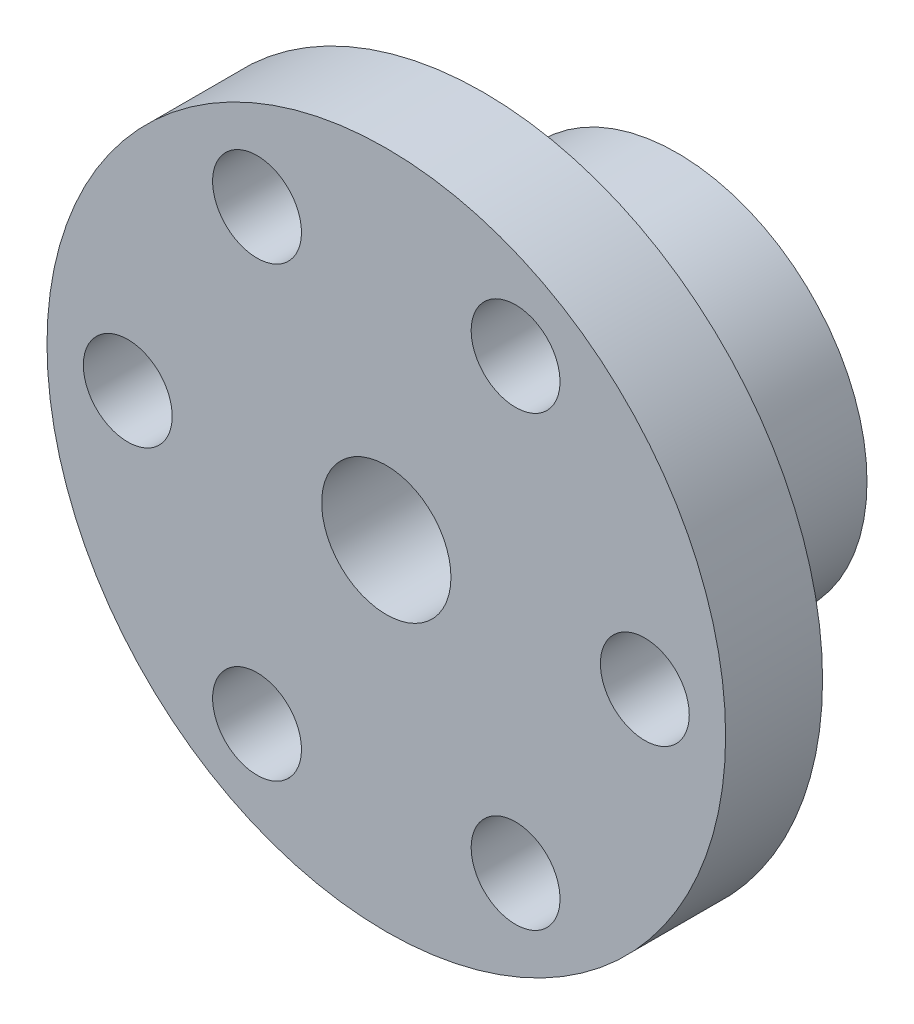
SolidWorks part; units mm, degrees
ref_plane "前视基准面" through (0, 0, 0) normal (0, 0, 1) x (1, 0, 0)
ref_plane "上视基准面" through (0, 0, 0) normal (0, 1, 0) x (1, 0, 0)
ref_plane "右视基准面" through (0, 0, 0) normal (1, 0, 0) x (0, 0, -1)
sketch "草图1" plane through (0, 0, 0) normal (0, 0, 1) x (1, 0, 0)
  line L0 (0, 0) -> (16, 0) construction
  line L1 (0, 0) -> (0, -16) construction
  line L2 (0, 0) -> (11.3137, 11.3137) construction
  line L3 (0, 0) -> (-11.3137, 11.3137) construction
  line L4 (0, 0) -> (6.1229, -14.7821) construction
  line L5 (-8, 13.8564) -> (0, 0) construction
  line L6 (0, 0) -> (8, 13.8564) construction
  line L7 (-16.5, -12.9904) -> (-16.5, 12.9904)
  line L8 (16.5, 12.9904) -> (16.5, -12.9904)
  line L9 (0, 0) -> (1.8478, 0.7654)
  line L10 (1.8478, 0.7654) -> (9.8841, -18.6361)
  line L11 (9.8841, -18.6361) -> (8.0364, -19.4015)
  line L12 (1.4782, 0.6123) -> (7.2185, -13.2459)
  line L13 (7.2185, -13.2459) -> (7.588, -13.0928)
  line L14 (-12.5, -16.8745) -> (-12.5, 16.8745)
  line L15 (12.5, 16.8745) -> (12.5, -16.8745)
  circle A0 centre (0, 0) radius 21
  circle A1 centre (0, 0) radius 16 construction
  circle A2 centre (11.3137, 11.3137) radius 2.75
  circle A3 centre (-11.3137, 11.3137) radius 2.75
  circle A4 centre (0, 16) radius 2.75
  circle A5 centre (-8, 13.8564) radius 2.75
  circle A6 centre (8, 13.8564) radius 2.75
  circle A7 centre (0, 0) radius 4
  point P21 (0, 21)
  dimension "D1" = 90
  dimension "D6" = 42
  dimension "(D4)" = 32
  dimension "D5" = 5.5
  dimension "D2" = 3.2
  dimension "(d)" = 8
  dimension "JD" = 22.5
  dimension "D3" = 60
  dimension "D4" = 6
  dimension "L5" = 33
  dimension "Q" = 4
  dimension "L6" = 25
sketch "草图2" plane through (0, 0, 0) normal (1, 0, 0) x (0, 0, -1)
  line L0 (-3, 0) -> (15, 0) construction
  line L1 (-3, 0) -> (-3, 21)
  line L2 (-3, 21) -> (3, 21)
  line L3 (3, 21) -> (3, 11.75)
  line L4 (3, 11.75) -> (15, 11.75)
  line L5 (15, 11.75) -> (15, 0)
  line L6 (0, 0) -> (0, 21) construction
  line L7 (8, 11.75) -> (8, 0)
  line L8 (-75, 0) -> (75, 0) construction
  line L9 (75, 0) -> (-57, 0)
  dimension "D1" = 23.5
  dimension "L1" = 18
  dimension "L2" = 6
  dimension "L7" = 5
  dimension "ZL" = 150
  dimension "D3" = 132
sketch "草图3" plane through (0, 0, 0) normal (1, 0, 0) x (0, 0, -1)
  line L0 (-3, 0) -> (-3, 21) construction
  line L1 (-3, 21) -> (3, 21) construction
  line L2 (3, 21) -> (3, 11.75) construction
  line L3 (3, 11.75) -> (15, 11.75) construction
  line L4 (15, 11.75) -> (15, 0) construction
  line L5 (-3, 0) -> (-3, 21)
  line L6 (-3, 21) -> (3, 21)
  line L7 (3, 21) -> (3, 11.75)
  line L8 (3, 11.75) -> (15, 11.75)
  line L9 (15, 11.75) -> (15, 0)
  line L10 (-3, 0) -> (15, 0)
revolve "旋转1" add sketch "草图3" angle 360 about L10
sketch "草图13" [suppressed] plane through (0, 0, 0) normal (0, 0, 1) x (1, 0, 0)
  line L0 (-12.5, -9.1652) -> (-12.5, 9.1652) construction
  line L1 (12.5, 9.1652) -> (12.5, -9.1652) construction
  line L2 (-12.5, -9.1652) -> (-12.5, 9.1652)
  line L3 (12.5, 9.1652) -> (12.5, -9.1652)
  circle A0 centre (0, 0) radius 15.5 construction
  arc A1 (-12.5, 9.1652) -> (-12.5, -9.1652) centre (0, 0) ccw
  arc A2 (12.5, -9.1652) -> (12.5, 9.1652) centre (0, 0) ccw
extrude "切除-拉伸7" [suppressed] cut sketch "草图13" along normal up to vertex from vertex
sketch "草图5" [suppressed] plane through (0, 0, 0) normal (0, 0, 1) x (1, 0, 0)
  circle A0 centre (-8.1317, 8.1317) radius 1.7 construction
  circle A1 centre (8.1317, 8.1317) radius 1.7 construction
  circle A2 centre (-8.1317, 8.1317) radius 1.7
  circle A3 centre (8.1317, 8.1317) radius 1.7
extrude "切除-拉伸2" [suppressed] cut sketch "草图5" along normal up to vertex from vertex
mirror "镜向1" [suppressed] about plane through (0, 0, 0) normal (0, 1, 0)
sketch "草图6" [suppressed] plane through (0, 0, 0) normal (0, 0, 1) x (1, 0, 0)
  circle A0 centre (0, 11.5) radius 1.7 construction
  circle A1 centre (0, 11.5) radius 1.7
extrude "切除-拉伸3" [suppressed] cut sketch "草图6" along normal up to vertex from vertex
mirror "镜向2" [suppressed] about plane through (0, 0, 0) normal (0, 1, 0)
sketch "草图7" [suppressed] plane through (0, 0, 0) normal (0, 0, 1) x (1, 0, 0)
  circle A0 centre (-5.75, 9.9593) radius 1.7 construction
  circle A1 centre (5.75, 9.9593) radius 1.7 construction
  circle A2 centre (-5.75, 9.9593) radius 1.7
  circle A3 centre (5.75, 9.9593) radius 1.7
extrude "切除-拉伸4" [suppressed] cut sketch "草图7" along normal up to vertex from vertex
mirror "镜向3" [suppressed] about plane through (0, 0, 0) normal (0, 1, 0)
sketch "草图14" [suppressed] plane through (0, 0, 0) normal (0, 0, 1) x (1, 0, 0)
  line L0 (-10, -11.8427) -> (-10, 11.8427) construction
  line L1 (10, 11.8427) -> (10, -11.8427) construction
  line L2 (-10, -11.8427) -> (-10, 11.8427)
  line L3 (10, 11.8427) -> (10, -11.8427)
  circle A0 centre (0, 0) radius 15.5 construction
  arc A1 (-10, 11.8427) -> (-10, -11.8427) centre (0, 0) ccw
  arc A2 (10, -11.8427) -> (10, 11.8427) centre (0, 0) ccw
extrude "切除-拉伸8" [suppressed] cut sketch "草图14" along normal up to vertex from vertex
sketch "草图8" plane through (0, 0, 0) normal (0, 0, 1) x (1, 0, 0)
  circle A0 centre (0, 0) radius 4 construction
  circle A1 centre (0, 0) radius 4
extrude "切除-拉伸5" cut sketch "草图8" against normal through all and the other way through all
cosmetic thread "装饰螺纹线2" parameters "D2"=8.1
sketch "草图11" plane through (0, 0, 0) normal (1, 0, 0) x (0, 0, -1)
  line L0 (8, 11.75) -> (8, -11.75)
  line L1 (3, -11.75) -> (15, -11.75) construction
split line "分割线1"
sketch "草图10" plane through (0, 0, 0) normal (0, 0, 1) x (1, 0, 0)
  circle A0 centre (0, 0) radius 4 construction
  circle A1 centre (0, 0) radius 4
extrude "凸台-拉伸1" add sketch "草图10" along normal up to vertex (75 mm away) from vertex separate body up to point (0, 0, 75) starting at point (0, 0, -75)
cosmetic thread "装饰螺纹线3" parameters "D2"=6.8
sketch "草图12" plane through (0, 0, 3) normal (0, 0, 1) x (1, 0, 0)
  circle A0 centre (16, 0) radius 2.75
  circle A1 centre (-11.3137, 11.3137) radius 2.75 construction
extrude "切除-拉伸6" cut sketch "草图12" against normal up to vertex (6 mm away) up to point (0, 21, -3)
pattern_circular "阵列(圆周)1" count 6 over 360 about axis through (0, 0, 3) along (0, 0, 1) of "切除-拉伸6"
delete or keep bodies "实体-删除1" type delete bodies bodies 111
